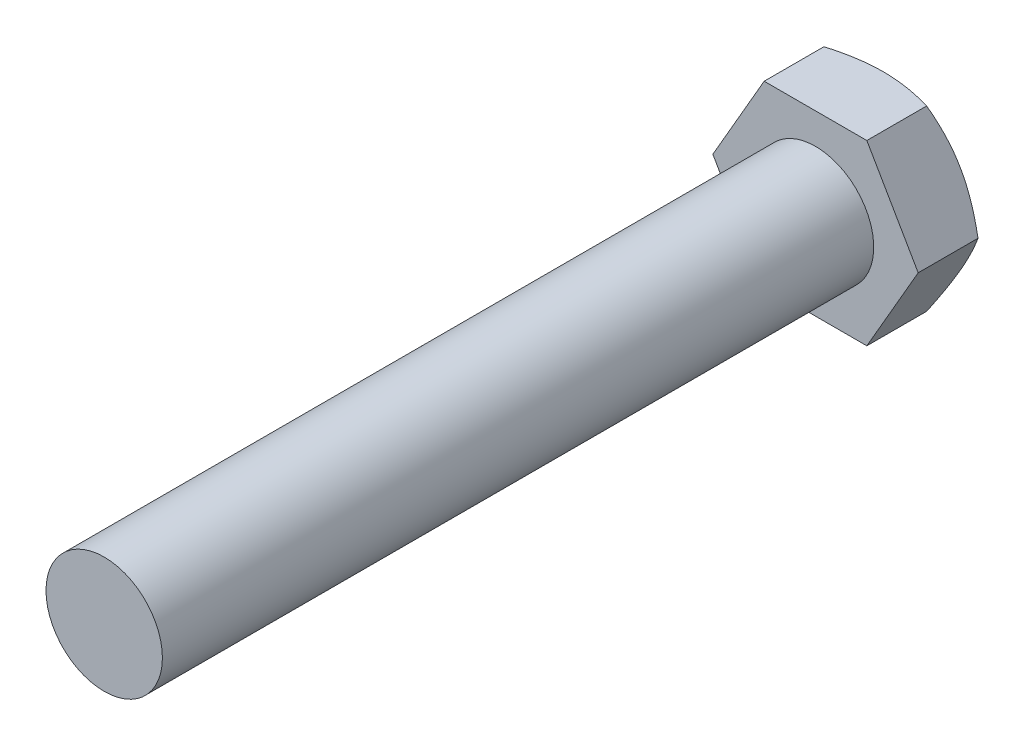
SolidWorks part; units mm, degrees
ref_plane "前视" through (0, 0, 0) normal (0, 0, 1) x (1, 0, 0)
ref_plane "上视" through (0, 0, 0) normal (0, 1, 0) x (1, 0, 0)
ref_plane "右视" through (0, 0, 0) normal (1, 0, 0) x (0, 0, -1)
sketch "草图1" plane through (0, 0, 0) normal (0, 0, 1) x (1, 0, 0)
  line L1 (31.7543, 0) -> (15.8771, 27.5)
  line L2 (15.8771, 27.5) -> (-15.8771, 27.5)
  line L3 (-15.8771, 27.5) -> (-31.7543, 0)
  line L4 (-31.7543, 0) -> (-15.8771, -27.5)
  line L5 (-15.8771, -27.5) -> (15.8771, -27.5)
  line L6 (15.8771, -27.5) -> (31.7543, 0)
  circle A0 centre (0, 0) radius 27.5 construction
  dimension "D1" = 55
extrude "拉伸1" add sketch "草图1" along normal blind 22.5
sketch "草图2" plane through (0, 0, 22.5) normal (0, 0, 1) x (1, 0, 0)
  circle A0 centre (0, 0) radius 18
  dimension "D1" = 36
extrude "拉伸2" add sketch "草图2" along normal blind 220
sketch "草图3" plane through (0, 0, 0) normal (0, 1, 0) x (1, 0, 0)
  line L0 (-43.0164, -4) -> (48.8375, -4) construction
  line L1 (0, 27.6095) -> (0, -28.6699) construction
  line L2 (31.7543, -22.5) -> (31.7543, 0) construction
  line L3 (31.7543, -22.5) -> (31.7543, 0) construction
  line L4 (31.7543, -4) -> (4.6012, 11.6768)
  line L5 (4.6012, 11.6768) -> (47.2449, 19.8752)
  line L6 (47.2449, 19.8752) -> (31.7543, -4)
  dimension "D1" = 4
  dimension "D2" = 30
revolve "切除-旋转1" cut sketch "草图3" angle 360 about L1
sketch "草图4" plane through (0, 0, 0) normal (0, 1, 0) x (1, 0, 0)
  line L0 (16, -242.5) -> (16, -242.8)
  line L1 (-18, -242.5) -> (18, -242.5) construction
  line L2 (16, -242.8) -> (19.2868, -246.0868)
  line L3 (19.2868, -246.0868) -> (19.2868, -239.2132)
  line L4 (19.2868, -239.2132) -> (16, -242.5)
  line L5 (0, -242.5) -> (0, -22.5) construction
  dimension "D1" = 16
  dimension "D2" = 0.3
  dimension "D3" = 45
  dimension "D4" = 45
sketch "草图5" plane through (0, 0, 242.5) normal (0, 0, 1) x (1, 0, 0)
  circle A0 centre (0, 0) radius 18 construction
  circle A1 centre (0, 0) radius 18
curve "螺旋线/涡状线1" pitch 4 height 85 turns 21.25
sweep "切除-扫描1" [suppressed] cut profiles "草图4" path "螺旋线/涡状线1"
sketch "草图6" plane through (0, 0, 0) normal (0, 1, 0) x (1, 0, 0)
  line L0 (0, -242.5) -> (0, -22.5) construction
  line L1 (16, -155) -> (26.0877, -155)
  line L2 (16, -155) -> (16, -158)
  line L3 (16, -158) -> (26.0877, -158)
  line L4 (26.0877, -155) -> (26.0877, -158)
  line L6 (24.8261, 0) -> (-24.8261, 0) construction
  dimension "D1" = 3
  dimension "D2" = 16
  dimension "D3" = 155
revolve "切除-旋转2" [suppressed] cut sketch "草图6" angle 360
fillet "圆角1" [suppressed] radius 1
